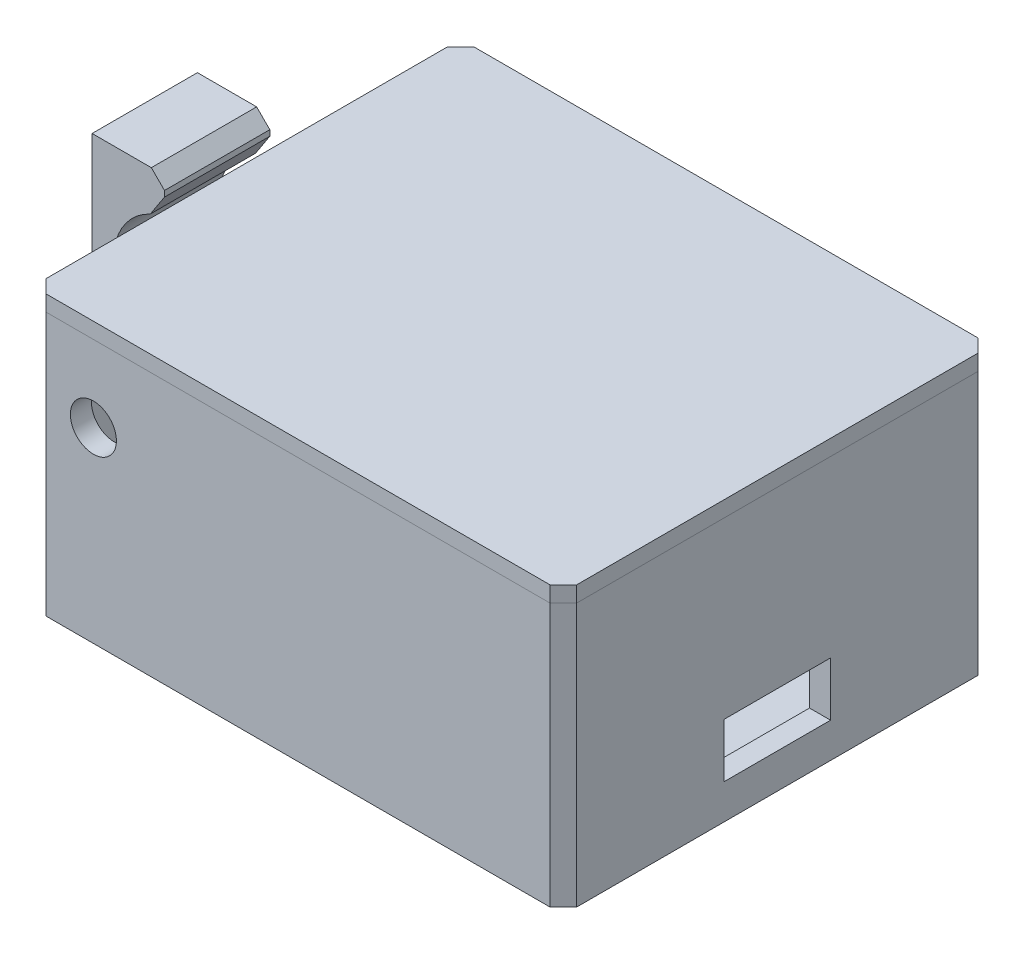
SolidWorks part; units mm, degrees
note: The reader was unsure of these and kept them because the rebuilt part matched: shared geometry of "Sketch2<3>".
ref_plane "Front Plane" through (0, 0, 0) normal (0, 0, 1) x (1, 0, 0)
ref_plane "Top Plane" through (0, 0, 0) normal (0, 1, 0) x (1, 0, 0)
ref_plane "Right Plane" through (0, 0, 0) normal (1, 0, 0) x (0, 0, -1)
sketch "Sketch1" plane through (0, 0, 0) normal (0, 1, 0) x (1, 0, 0)
  line L1 (18.3, -14.4) -> (-18.3, -14.4) construction
  line L2 (18.3, -14.4) -> (18.3, 14.4) construction
  line L3 (18.3, 14.4) -> (-18.3, 14.4) construction
  line L4 (-18.3, -14.4) -> (-18.3, 14.4) construction
  line L5 (18.3, -14.4) -> (-18.3, 14.4) construction
  line L6 (18.3, 14.4) -> (-18.3, -14.4) construction
  point P0 (0, 0)
  dimension "D1" = 36.6
  dimension "D2" = 28.8
sketch "Sketch2" plane through (0, 0, 0) normal (0, 1, 0) x (1, 0, 0)
  line L4 (-20.15, -16.25) -> (20.15, -16.25)
  line L5 (20.15, -16.25) -> (20.15, 16.25)
  line L6 (20.15, 16.25) -> (-20.15, 16.25)
  line L7 (-20.15, 16.25) -> (-20.15, -16.25)
  line L8 (-18.55, -14.65) -> (18.55, -14.65)
  line L9 (18.55, -14.65) -> (18.55, 14.65)
  line L10 (-18.55, 14.65) -> (-18.55, -14.65)
  line L11 (18.55, 14.65) -> (-18.55, 14.65)
  line L12 (-18.55, -14.65) -> (18.55, -14.65)
  line L13 (18.55, -14.65) -> (18.55, 14.65)
  line L14 (-18.55, 14.65) -> (-18.55, -14.65)
  line L15 (18.55, 14.65) -> (-18.55, 14.65)
  dimension "D1" = 0.25
  dimension "D2" = 1.6
extrude "Boss-Extrude1" add sketch "Sketch2" along normal blind 1.2 contours L4 L5 L6 L7
extrude "Boss-Extrude2" add sketch "Sketch2<3>" along normal blind 20
sketch "Sketch2<3>" plane through (0, 0, 0) normal (0, 1, 0) x (1, 0, 0) same geometry as "Sketch2"
sketch "Sketch3" plane through (20.15, 0, 0) normal (1, 0, 0) x (0, 0, -1)
  line L0 (0, 20) -> (0, 0) construction
  line L1 (-16.25, 20) -> (16.25, 20) construction
  line L2 (-16.25, 0) -> (16.25, 0) construction
  line L3 (14.65, 1.2) -> (-14.65, 1.2) construction
  line L4 (14.65, 1.2) -> (-14.65, 1.2) construction
  line L6 (4.05, 2.65) -> (-4.05, 2.65)
  line L7 (4.05, 2.65) -> (4.05, 6.75)
  line L8 (4.05, 6.75) -> (-4.05, 6.75)
  line L9 (-4.05, 2.65) -> (-4.05, 6.75)
  line L10 (4.05, 2.65) -> (-4.05, 6.75) construction
  line L11 (4.05, 6.75) -> (-4.05, 2.65) construction
  point P8 (0, 4.7)
  dimension "D1" = 1.45
  dimension "D2" = 8.1
  dimension "D3" = 4.1
extrude "Cut-Extrude1" cut sketch "Sketch3" against normal up to next
chamfer "Chamfer1" distance 1 angle 45 4 edges at (20.15, 10, 16.25) (-20.15, 10, 16.25) (-20.15, 10, -16.25) (20.15, 10, -16.25)
sketch "Sketch4" plane through (-20.15, 0, 0) normal (-1, 0, 0) x (0, 0, 1)
  line L1 (-2.2522, 0) -> (-10.2522, 0)
  line L2 (-2.2522, 0) -> (-2.2522, 15)
  line L3 (-2.2522, 15) -> (-10.2522, 15)
  line L4 (-10.2522, 0) -> (-10.2522, 15)
  line L5 (-2.2522, 0) -> (-10.2522, 15) construction
  line L6 (-2.2522, 15) -> (-10.2522, 0) construction
  line L10 (-6.2522, 15) -> (-6.2522, -5) construction
  line L12 (-15.25, 0) -> (15.25, 0) construction
  point P0 (-6.2522, 7.5)
  point P9 (0, 0)
  dimension "D1" = 8
  dimension "D2" = 15
extrude "Boss-Extrude3" add sketch "Sketch4" along normal blind 15
sketch "Sketch5" plane through (0, 0, -2.2522) normal (0, 0, 1) x (1, 0, 0)
  line L0 (-35.15, 7.5) -> (-27.65, 7.5) construction
  line L1 (-35.15, 0) -> (-35.15, 15) construction
  line L2 (-27.65, 7.5) -> (-27.65, 15) construction
  line L3 (-35.15, 15) -> (-20.15, 15) construction
  line L4 (-28.65, 12.2713) -> (-28.65, 15)
  line L5 (-28.65, 15) -> (-26.65, 15)
  line L6 (-26.65, 15) -> (-26.65, 12.2713)
  arc A0 (-28.65, 12.2713) -> (-26.65, 12.2713) centre (-27.65, 7.5) ccw
  dimension "D1" = 9.75
  dimension "D2" = 2
extrude "Cut-Extrude3" cut sketch "Sketch5" against normal up to next contours A0 L6 L5 L4
chamfer "Chamfer2" distance 1 angle 45 4 edges at (-26.65, 12.2713, -6.2522) (-28.65, 12.2713, -6.2522) (-28.65, 15, -6.2522) (-26.65, 15, -6.2522)
chamfer "Chamfer3" distance 1 angle 45 5 edges at (-20.15, 7.5, -10.2522) (-20.15, 7.5, -2.2522) (-35.15, 7.5, -10.2522) (-35.15, 7.5, -2.2522) (-35.15, 15, -6.2522)
sketch "Sketch6" plane through (0, 0, 14.65) normal (0, 0, -1) x (-1, 0, 0)
  line L0 (-17.4162, 17.5) -> (17.4162, 17.5) construction
  line L1 (18.55, 20) -> (-18.55, 20) construction
  line L2 (0, 17.5) -> (0, 20) construction
  line L3 (-6.5, 16.5) -> (-11.5, 16.5)
  line L4 (-6.5, 16.5) -> (-6.5, 18.5)
  line L5 (-6.5, 18.5) -> (-11.5, 18.5)
  line L6 (-11.5, 16.5) -> (-11.5, 18.5)
  line L7 (-6.5, 16.5) -> (-11.5, 18.5) construction
  line L8 (-6.5, 18.5) -> (-11.5, 16.5) construction
  line L13 (6.5, 18.5) -> (11.5, 18.5)
  line L14 (11.5, 16.5) -> (11.5, 18.5)
  line L15 (6.5, 16.5) -> (11.5, 16.5)
  line L16 (6.5, 16.5) -> (6.5, 18.5)
  point P4 (-9, 17.5)
  point P10 (0, 0)
  dimension "D1" = 2.5
  dimension "D2" = 5
  dimension "D3" = 2
  dimension "D4" = 9
extrude "Cut-Extrude4" cut sketch "Sketch6" against normal blind 0.4
chamfer "Chamfer4" distance 0.4 angle 45 2 edges at (9, 18.5, 15.05) (-9, 18.5, 15.05)
mirror "Mirror1" about plane through (0, 0, 0) normal (0, 0, 1) of "Chamfer4", "Cut-Extrude4"
sketch "Sketch7" plane through (0, 20, 0) normal (0, 1, 0) x (1, 0, 0)
  line L0 (18.55, -14.65) -> (18.55, 14.65) construction
  line L1 (-18.55, -14.65) -> (18.55, -14.65) construction
  line L2 (-18.55, 14.65) -> (-18.55, -14.65) construction
  line L3 (18.55, 14.65) -> (-18.55, 14.65) construction
  line L4 (18.55, -14.65) -> (18.55, 14.65)
  line L5 (-18.55, -14.65) -> (18.55, -14.65)
  line L6 (-18.55, 14.65) -> (-18.55, -14.65)
  line L7 (18.55, 14.65) -> (-18.55, 14.65)
  line L8 (-21.15, 10.2522) -> (-21.15, 2.2522)
  line L18 (-20.15, 15.25) -> (-20.15, -15.25)
  line L19 (-20.15, -15.25) -> (-19.15, -16.25)
  line L20 (-19.15, -16.25) -> (19.15, -16.25)
  line L21 (19.15, -16.25) -> (20.15, -15.25)
  line L22 (20.15, -15.25) -> (20.15, 15.25)
  line L23 (20.15, 15.25) -> (19.15, 16.25)
  line L24 (19.15, 16.25) -> (-19.15, 16.25)
  line L25 (-19.15, 16.25) -> (-20.15, 15.25)
  line L32 (-20.15, 15.25) -> (-20.15, -15.25)
  line L33 (-20.15, -15.25) -> (-19.15, -16.25)
  line L34 (-19.15, -16.25) -> (19.15, -16.25)
  line L35 (19.15, -16.25) -> (20.15, -15.25)
  line L36 (20.15, -15.25) -> (20.15, 15.25)
  line L37 (20.15, 15.25) -> (19.15, 16.25)
  line L38 (19.15, 16.25) -> (-19.15, 16.25)
  line L39 (-19.15, 16.25) -> (-20.15, 15.25)
  dimension "D1" = 0
extrude "Boss-Extrude4" add sketch "Sketch7" along normal blind 1.2 separate body
sketch "Sketch8" plane through (0, 20, 0) normal (0, -1, 0) x (1, 0, 0)
  line L0 (18.3, -14.4) -> (-18.3, -14.4) construction
  line L1 (18.3, 14.4) -> (18.3, -14.4) construction
  line L2 (-18.3, 14.4) -> (-18.3, -14.4) construction
  line L3 (18.3, 14.4) -> (-18.3, 14.4) construction
  line L4 (18.3, -14.4) -> (-18.3, -14.4)
  line L5 (18.3, 14.4) -> (18.3, -14.4)
  line L6 (-18.3, 14.4) -> (-18.3, -14.4)
  line L7 (18.3, 14.4) -> (-18.3, 14.4)
  line L8 (17.5, -13.6) -> (-17.5, -13.6)
  line L9 (-17.5, 13.6) -> (-17.5, -13.6)
  line L10 (17.5, 13.6) -> (-17.5, 13.6)
  line L11 (17.5, 13.6) -> (17.5, -13.6)
  dimension "D1" = 0.8
extrude "Boss-Extrude5" add sketch "Sketch8" along normal blind 1.2
sketch "Sketch10" plane through (0, 20, 0) normal (0, -1, 0) x (1, 0, 0)
  line L1 (-11.5, 13.2) -> (-6.5, 13.2)
  line L2 (-11.5, 13.2) -> (-11.5, 14.4)
  line L3 (-11.5, 14.4) -> (-6.5, 14.4)
  line L4 (-6.5, 13.2) -> (-6.5, 14.4)
  line L5 (-11.5, 13.2) -> (-6.5, 14.4) construction
  line L6 (-11.5, 14.4) -> (-6.5, 13.2) construction
  line L7 (18.3, 14.4) -> (-18.3, 14.4) construction
  line L8 (0, 12.798) -> (0, 9.3186) construction
  line L9 (11.5, 14.4) -> (6.5, 14.4)
  line L10 (6.5, 13.2) -> (6.5, 14.4)
  line L11 (11.5, 13.2) -> (6.5, 13.2)
  line L12 (11.5, 13.2) -> (11.5, 14.4)
  line L13 (-11.5, 15.05) -> (-11.5, 14.65) construction
  line L14 (-11.5, 15.05) -> (-11.5, 14.65) construction
  point P4 (-9, 13.8)
  point P15 (0, 0)
  dimension "D1" = 1.2
  dimension "D2" = 9
  dimension "D3" = 5
extrude "Boss-Extrude6" add sketch "Sketch10" along normal blind 3.5 contours L11 L10 L9 L12
sketch "Sketch13" plane through (6.5, 0, 0) normal (-1, 0, 0) x (0, 0, 1)
  line L0 (15, 18.0793) -> (14.4, 18.6793)
  line L2 (15.05, 18.1) -> (14.65, 18.5) construction
  line L3 (14.4, 18.6793) -> (14.4, 16.5)
  line L5 (15, 17.1) -> (15, 18.0793)
  line L6 (14.65, 20) -> (14.65, 1.2) construction
  line L7 (15, 17.1) -> (14.4, 16.5)
  line L8 (14.4, 16.5) -> (14.4, 18.8) construction
  point P1 (14.4, 11.647)
  point P10 (0, 0)
  point P11 (15.05, 12.0314)
  point P15 (14.4, 13.6793)
  dimension "D1" = 0.35
  dimension "D2" = 0.05
extrude "Boss-Extrude7" add sketch "Sketch13" against normal up to surface (5 mm away) up to face at (11.5, 18.4333, 13.7333)
ref_plane "Plane2" through (0, 0, 0) normal (-1, 0, 0) x (0, 0, 1)
mirror "Mirror6" about plane through (0, 0, 0) normal (-1, 0, 0) of "Boss-Extrude6", "Boss-Extrude7"
mirror "Mirror7" about plane through (0, 0, 0) normal (0, 0, 1) of "Mirror6", "Boss-Extrude6", "Boss-Extrude7"
ref_plane "Plane3" through (0, 11.2, 0) normal (0, 1, 0) x (1, 0, 0)
sketch "Sketch15" plane through (0, 0, 14.65) normal (0, 0, -1) x (-1, 0, 0)
  line L0 (16.115, 11.2) -> (-16.115, 11.2) construction
  line L1 (18.55, 20) -> (18.55, 1.2) construction
  circle A0 centre (15.55, 14.2) radius 1.75
  dimension "D1" = 3.5
  dimension "D2" = 3
  dimension "D3" = 3
extrude "Cut-Extrude6" cut sketch "Sketch15" against normal up to next (1.6 mm away)
chamfer "Chamfer6" distance 3 angle 30 1 edges at (-20.15, 15, -6.2522)
equation "\"D1@Sketch3\"=1.45mm"
